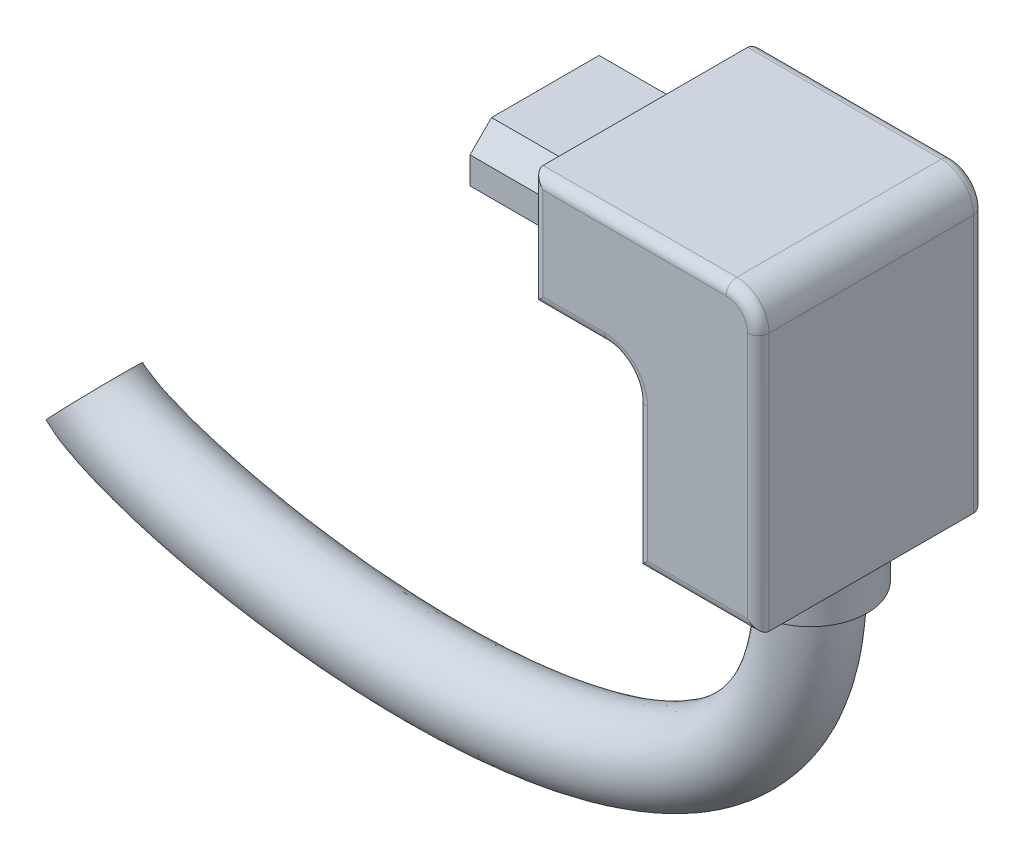
SolidWorks part; units mm, degrees
ref_plane "前视基准面" through (0, 0, 0) normal (0, 0, 1) x (1, 0, 0)
ref_plane "上视基准面" through (0, 0, 0) normal (0, 1, 0) x (1, 0, 0)
ref_plane "右视基准面" through (0, 0, 0) normal (1, 0, 0) x (0, 0, -1)
sketch "草图1" plane through (0, 0, 0) normal (0, 0, 1) x (1, 0, 0)
  line L0 (0, 27) -> (0, 0)
  line L1 (-11.3, 16.4) -> (-21, 16.4)
  line L3 (0, 27) -> (-21, 27)
  line L4 (-21, 16.4) -> (-21, 27)
  line L7 (0, 0) -> (-11.3, 0)
  line L8 (-11.3, 16.4) -> (-11.3, 0)
  dimension "D1" = 27
  dimension "D2" = 21
  dimension "D3" = 10.6
  dimension "D4" = 11.3
extrude "凸台-拉伸1" add sketch "草图1" along normal mid plane 21
sketch "草图2" plane through (-21, 0, 0) normal (-1, 0, 0) x (0, 0, 1)
  line L0 (0, 16.4) -> (0, 27) construction
  line L1 (10.5, 16.4) -> (-10.5, 16.4) construction
  line L2 (10.5, 27) -> (-10.5, 27) construction
  line L3 (-5, 23.95) -> (-7, 21.95)
  line L4 (7, 19.45) -> (-7, 19.45)
  line L5 (7, 19.45) -> (7, 21.95)
  line L6 (5, 23.95) -> (-5, 23.95)
  line L7 (-7, 19.45) -> (-7, 21.95)
  line L8 (7, 19.45) -> (-7, 23.95) construction
  line L9 (7, 23.95) -> (-7, 19.45) construction
  line L10 (7, 21.95) -> (5, 23.95)
  point P6 (0, 21.7)
  dimension "D1" = 14
  dimension "D2" = 4.5
extrude "凸台-拉伸2" add sketch "草图2" along normal blind 9.3
fillet "圆角1" radius 3 2 edges at (-11.3, 16.4, 0) (0, 27, 0)
fillet "圆角2" radius 1 16 edges at (-21, 21.7, -10.5) (-17.65, 16.4, -10.5) (-12.1787, 15.5213, -10.5) (-11.3, 6.7, -10.5) (-5.65, 0, -10.5) (0, 12, -10.5) (-0.8787, 26.1213, -10.5) (-12, 27, -10.5) (-5.65, 0, 10.5) (-11.3, 6.7, 10.5) (-12.1787, 15.5213, 10.5) (-17.65, 16.4, 10.5) (-21, 21.7, 10.5) (-12, 27, 10.5) (-0.8787, 26.1213, 10.5) (0, 12, 10.5)
sketch "草图4" plane through (0, 0, 0) normal (0, -1, 0) x (1, 0, 0)
  line L0 (0, 9.5) -> (0, -9.5) construction
  line L1 (0, 9.5) -> (-11.3, 9.5) construction
  circle A0 centre (-5.65, 0) radius 5.25
  point P5 (0, 0)
  point P9 (-5.65, 9.5)
  dimension "D1" = 10.5
extrude "凸台-拉伸3" add sketch "草图4" along normal blind 3.5
sketch "草图5" plane through (0, -3.5, 0) normal (0, -1, 0) x (1, 0, 0)
  circle A0 centre (-5.65, 0) radius 3.7
  dimension "D1" = 7.4
sketch "草图6" plane through (0, 0, 0) normal (0, 0, 1) x (1, 0, 0)
  line L0 (-9.35, -3.5) -> (-1.95, -3.5) construction
  line L1 (-54.9225, -28.4) -> (-18.8498, -28.4) construction
  line L2 (-21, 27) -> (-3, 27) construction
  spline S0 degree 3 poles (-5.65, -3.5) (-5.65, -38.8777) (-65.2474, -28.1778) (-72.2101, -21.5366) knots 0 0 0 0 1 1 1 1
  dimension "D1" = 55.4
sweep "扫描1" add profiles "草图5" path "草图6"
